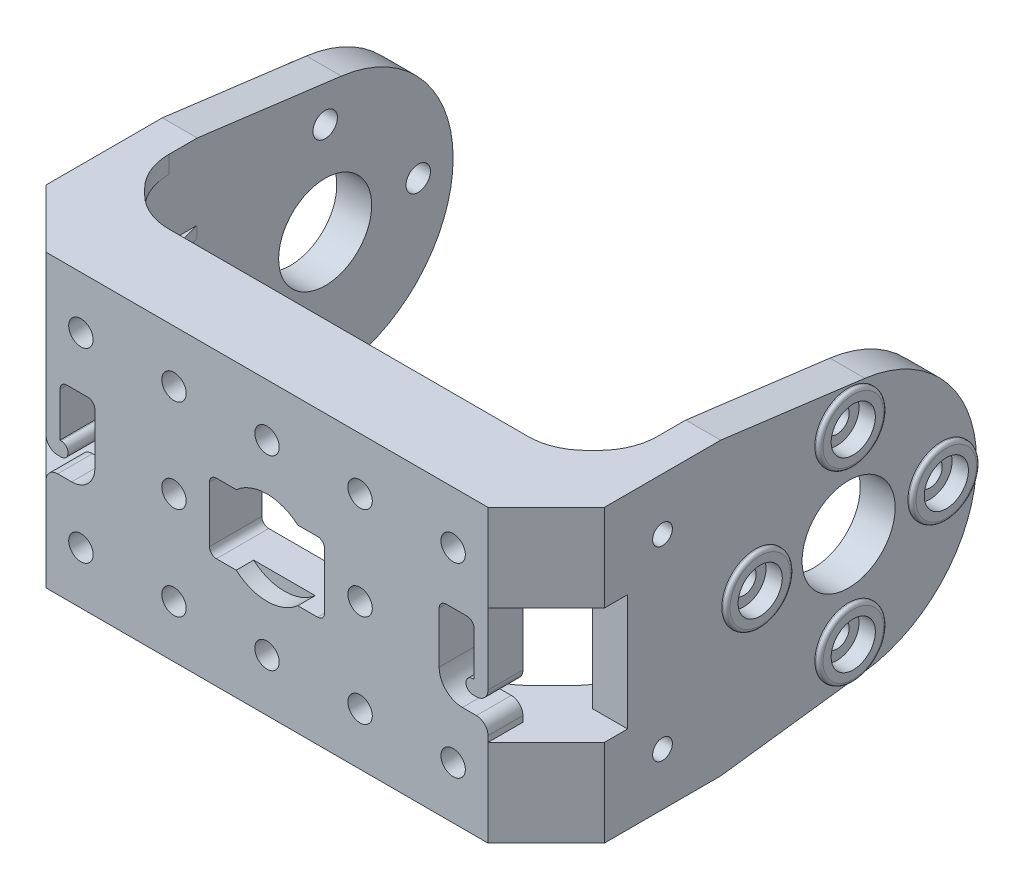
SolidWorks part; units mm, degrees
ref_plane "Plan de face" through (0, 0, 0) normal (0, 0, 1) x (1, 0, 0)
ref_plane "Plan de dessus" through (0, 0, 0) normal (0, 1, 0) x (1, 0, 0)
ref_plane "Plan de droite" through (0, 0, 0) normal (1, 0, 0) x (0, 0, -1)
ref_plane "Plan1" through (0, 0, 23) normal (0, 0, 1) x (1, 0, 0)
sketch "Esquisse1" plane through (0, 0, 23) normal (0, 0, 1) x (1, 0, 0)
  line L0 (14.5956, -5) -> (10.0809, -3.5)
  line L1 (10.0809, -3.5) -> (10.0809, -2.4936)
  line L2 (10.0809, -2.4936) -> (11.2, -1.8475)
  line L3 (11.2, -1.8475) -> (11.2, 1.8475)
  line L4 (11.2, 1.8475) -> (10.0809, 2.4936)
  line L5 (10.0809, 2.4936) -> (10.0809, 3.5)
  line L6 (10.0809, 3.5) -> (14.5956, 5)
  line L7 (14.5956, 5) -> (-14.5956, 5)
  line L8 (-14.5956, 5) -> (-10.0809, 3.5)
  line L9 (-10.0809, 3.5) -> (-10.0809, 2.4936)
  line L10 (-10.0809, 2.4936) -> (-11.2, 1.8475)
  line L11 (-11.2, 1.8475) -> (-11.2, -1.8475)
  line L12 (-11.2, -1.8475) -> (-10.0809, -2.4936)
  line L13 (-10.0809, -2.4936) -> (-10.0809, -3.5)
  line L14 (-10.0809, -3.5) -> (-14.5956, -5)
  line L15 (-14.5956, -5) -> (14.5956, -5)
extrude "Boss.-Extru.1" add sketch "Esquisse1" against normal blind 1
sketch "Esquisse2" plane through (0, 0, 22) normal (0, 0, -1) x (-1, 0, 0)
  line L0 (-14.5956, 5) -> (14.5956, 5)
  line L1 (14.5956, 5) -> (10.0809, 3.5)
  line L2 (10.0809, 3.5) -> (10.0809, -3.5)
  line L3 (10.0809, -3.5) -> (14.5956, -5)
  line L4 (14.5956, -5) -> (-14.5956, -5)
  line L5 (-14.5956, -5) -> (-10.0809, -3.5)
  line L6 (-10.0809, -3.5) -> (-10.0809, 3.5)
  line L7 (-10.0809, 3.5) -> (-14.5956, 5)
extrude "Boss.-Extru.2" add sketch "Esquisse2" along normal blind 0.5
sketch "Esquisse3" plane through (0, 0, 23) normal (0, 0, 1) x (1, 0, 0)
  line L0 (10.0809, 3.5) -> (8.3378, 3.5)
  line L1 (8.3378, 3.5) -> (10.0809, 2.4936)
  line L2 (10.0809, 2.4936) -> (10.0809, 3.5)
extrude "Enlèv. mat.-Extru.1" cut sketch "Esquisse3" against normal blind 1
sketch "Esquisse4" plane through (0, 0, 23) normal (0, 0, 1) x (1, 0, 0)
  line L0 (10.0809, -3.5) -> (10.0809, -2.4936)
  line L1 (10.0809, -2.4936) -> (8.3378, -3.5)
  line L2 (8.3378, -3.5) -> (10.0809, -3.5)
extrude "Enlèv. mat.-Extru.2" cut sketch "Esquisse4" against normal blind 1
sketch "Esquisse5" plane through (0, 0, 23) normal (0, 0, 1) x (1, 0, 0)
  line L0 (-10.0809, -3.5) -> (-8.3378, -3.5)
  line L1 (-8.3378, -3.5) -> (-10.0809, -2.4936)
  line L2 (-10.0809, -2.4936) -> (-10.0809, -3.5)
extrude "Enlèv. mat.-Extru.3" cut sketch "Esquisse5" against normal blind 1
sketch "Esquisse6" plane through (0, 0, 23) normal (0, 0, 1) x (1, 0, 0)
  line L0 (-10.0809, 3.5) -> (-10.0809, 2.4936)
  line L1 (-10.0809, 2.4936) -> (-8.3378, 3.5)
  line L2 (-8.3378, 3.5) -> (-10.0809, 3.5)
extrude "Enlèv. mat.-Extru.4" cut sketch "Esquisse6" against normal blind 1
sketch "Esquisse7" plane through (0, 5, 0) normal (0, 1, 0) x (-1, 0, 0)
  line L0 (21, 23) -> (21, 11)
  line L1 (21, 11) -> (19.5, 17.0147)
  line L2 (19.5, 17.0147) -> (17.5147, 19)
  line L3 (17.5147, 19) -> (-17.5147, 19)
  line L4 (-17.5147, 19) -> (-19.5, 17.0147)
  line L5 (-19.5, 17.0147) -> (-21, 11)
  line L6 (-21, 11) -> (-21, 23)
  line L7 (-21, 23) -> (21, 23)
extrude "Boss.-Extru.3" add sketch "Esquisse7" along normal blind 1
sketch "Esquisse8" plane through (0, -5, 0) normal (0, -1, 0) x (1, 0, 0)
  line L0 (-21, 11) -> (-21, 23)
  line L1 (-21, 23) -> (21, 23)
  line L2 (21, 23) -> (21, 11)
  line L3 (21, 11) -> (19.5, 17.0147)
  line L4 (19.5, 17.0147) -> (17.5147, 19)
  line L5 (17.5147, 19) -> (-17.5147, 19)
  line L6 (-17.5147, 19) -> (-19.5, 17.0147)
  line L7 (-19.5, 17.0147) -> (-21, 11)
extrude "Boss.-Extru.4" add sketch "Esquisse8" along normal blind 1
sketch "Esquisse9" plane through (0, 6, 0) normal (0, 1, 0) x (-1, 0, 0)
  line L0 (21, 23) -> (21, 11)
  line L1 (21, 11) -> (19.5, 17.0147)
  line L2 (19.5, 17.0147) -> (17.5147, 19)
  line L3 (17.5147, 19) -> (-17.5147, 19)
  line L4 (-17.5147, 19) -> (-19.5, 17.0147)
  line L5 (-19.5, 17.0147) -> (-21, 11)
  line L6 (-21, 11) -> (-21, 23)
  line L7 (-21, 23) -> (21, 23)
extrude "Boss.-Extru.5" add sketch "Esquisse9" along normal blind 5
sketch "Esquisse10" plane through (0, -6, 0) normal (0, -1, 0) x (1, 0, 0)
  line L0 (-21, 11) -> (-21, 23)
  line L1 (-21, 23) -> (21, 23)
  line L2 (21, 23) -> (21, 11)
  line L3 (21, 11) -> (19.5, 17.0147)
  line L4 (19.5, 17.0147) -> (17.5147, 19)
  line L5 (17.5147, 19) -> (-17.5147, 19)
  line L6 (-17.5147, 19) -> (-19.5, 17.0147)
  line L7 (-19.5, 17.0147) -> (-21, 11)
extrude "Boss.-Extru.6" add sketch "Esquisse10" along normal blind 5
sketch "Esquisse11" plane through (0, 11, 0) normal (0, 1, 0) x (-1, 0, 0)
  line L0 (21, 23) -> (21, 11)
  line L1 (21, 11) -> (19.5, 17.0147)
  line L2 (19.5, 17.0147) -> (17.5147, 19)
  line L3 (17.5147, 19) -> (-17.5147, 19)
  line L4 (-17.5147, 19) -> (-19.5, 17.0147)
  line L5 (-19.5, 17.0147) -> (-21, 11)
  line L6 (-21, 11) -> (-21, 23)
  line L7 (-21, 23) -> (21, 23)
extrude "Boss.-Extru.7" add sketch "Esquisse11" along normal blind 1.5
sketch "Esquisse12" plane through (0, 5, 0) normal (0, -1, 0) x (1, 0, 0)
  line L0 (-17.5147, 19) -> (17.5147, 19)
  line L1 (17.5147, 19) -> (15.0147, 21.5)
  line L2 (15.0147, 21.5) -> (-15.0147, 21.5)
  line L3 (-15.0147, 21.5) -> (-17.5147, 19)
extrude "Enlèv. mat.-Extru.5" cut sketch "Esquisse12" against normal blind 6
sketch "Esquisse13" plane through (0, -11, 0) normal (0, -1, 0) x (1, 0, 0)
  line L0 (-21, 11) -> (-21, 23)
  line L1 (-21, 23) -> (21, 23)
  line L2 (21, 23) -> (21, 11)
  line L3 (21, 11) -> (19.5, 17.0147)
  line L4 (19.5, 17.0147) -> (17.5147, 19)
  line L5 (17.5147, 19) -> (-17.5147, 19)
  line L6 (-17.5147, 19) -> (-19.5, 17.0147)
  line L7 (-19.5, 17.0147) -> (-21, 11)
extrude "Boss.-Extru.8" add sketch "Esquisse13" along normal blind 1.5
sketch "Esquisse14" plane through (-21, 0, 0) normal (-1, 0, 0) x (0, 0, 1)
  line L0 (23, 12.5) -> (23, 5)
  line L1 (23, 5) -> (19, 5)
  line L2 (19, 5) -> (19, -5)
  line L3 (19, -5) -> (23, -5)
  line L4 (23, -5) -> (23, -12.5)
  line L5 (23, -12.5) -> (11, -12.5)
  line L6 (11, -12.5) -> (-1.3986, -10.9107)
  line L7 (-1.3986, 10.9107) -> (11, 12.5)
  line L8 (11, 12.5) -> (23, 12.5)
  arc A0 (-1.3986, -10.9107) -> (-1.3986, 10.9107) centre (0, 0) cw
extrude "Boss.-Extru.9" add sketch "Esquisse14" along normal blind 3
sketch "Esquisse15" plane through (21, 0, 0) normal (1, 0, 0) x (0, 0, -1)
  line L0 (-23, 12.5) -> (-11, 12.5)
  line L1 (-11, 12.5) -> (1.3986, 10.9107)
  line L2 (1.3986, -10.9107) -> (-11, -12.5)
  line L3 (-11, -12.5) -> (-23, -12.5)
  line L4 (-23, -12.5) -> (-23, -5)
  line L5 (-23, -5) -> (-19, -5)
  line L6 (-19, -5) -> (-19, 5)
  line L7 (-19, 5) -> (-23, 5)
  line L8 (-23, 5) -> (-23, 12.5)
  arc A0 (1.3986, 10.9107) -> (1.3986, -10.9107) centre (0, 0) cw
extrude "Boss.-Extru.10" add sketch "Esquisse15" along normal blind 3
sketch "Esquisse16" plane through (0, -5, 0) normal (0, 1, 0) x (-1, 0, 0)
  line L0 (17.5147, 19) -> (15.0147, 21.5)
  line L1 (15.0147, 21.5) -> (-15.0147, 21.5)
  line L2 (-15.0147, 21.5) -> (-17.5147, 19)
  line L3 (-17.5147, 19) -> (17.5147, 19)
extrude "Enlèv. mat.-Extru.6" cut sketch "Esquisse16" against normal blind 6
sketch "Esquisse17" plane through (0, -12.5, 0) normal (0, -1, 0) x (1, 0, 0)
  line L0 (21, 15.5147) -> (19.5, 17.0147)
  line L1 (19.5, 17.0147) -> (21, 11)
  line L2 (21, 11) -> (21, 15.5147)
extrude "Enlèv. mat.-Extru.7" cut sketch "Esquisse17" against normal blind 1.5
sketch "Esquisse18" plane through (0, -12.5, 0) normal (0, -1, 0) x (1, 0, 0)
  line L0 (-19.5, 17.0147) -> (-21, 15.5147)
  line L1 (-21, 15.5147) -> (-21, 11)
  line L2 (-21, 11) -> (-19.5, 17.0147)
extrude "Enlèv. mat.-Extru.8" cut sketch "Esquisse18" against normal blind 1.5
sketch "Esquisse19" plane through (0, -11, 0) normal (0, -1, 0) x (1, 0, 0)
  line L0 (21, 22) -> (-21, 22)
  line L1 (-21, 22) -> (-21, 11)
  line L2 (-21, 11) -> (-19.5, 17.0147)
  line L3 (-19.5, 17.0147) -> (-15.0147, 21.5)
  line L4 (-15.0147, 21.5) -> (15.0147, 21.5)
  line L5 (15.0147, 21.5) -> (19.5, 17.0147)
  line L6 (19.5, 17.0147) -> (21, 11)
  line L7 (21, 11) -> (21, 22)
extrude "Enlèv. mat.-Extru.9" cut sketch "Esquisse19" against normal blind 5
sketch "Esquisse20" plane through (0, 12.5, 0) normal (0, 1, 0) x (-1, 0, 0)
  line L0 (-21, 11) -> (-19.5, 17.0147)
  line L1 (-19.5, 17.0147) -> (-21, 15.5147)
  line L2 (-21, 15.5147) -> (-21, 11)
extrude "Enlèv. mat.-Extru.10" cut sketch "Esquisse20" against normal blind 1.5
sketch "Esquisse21" plane through (0, 12.5, 0) normal (0, 1, 0) x (-1, 0, 0)
  line L0 (21, 11) -> (21, 15.5147)
  line L1 (21, 15.5147) -> (19.5, 17.0147)
  line L2 (19.5, 17.0147) -> (21, 11)
extrude "Enlèv. mat.-Extru.11" cut sketch "Esquisse21" against normal blind 1.5
sketch "Esquisse22" plane through (0, 11, 0) normal (0, 1, 0) x (-1, 0, 0)
  line L0 (21, 11) -> (21, 22)
  line L1 (21, 22) -> (-21, 22)
  line L2 (-21, 22) -> (-21, 11)
  line L3 (-21, 11) -> (-19.5, 17.0147)
  line L4 (-19.5, 17.0147) -> (-15.0147, 21.5)
  line L5 (-15.0147, 21.5) -> (15.0147, 21.5)
  line L6 (15.0147, 21.5) -> (19.5, 17.0147)
  line L7 (19.5, 17.0147) -> (21, 11)
extrude "Enlèv. mat.-Extru.12" cut sketch "Esquisse22" against normal blind 5
sketch "Esquisse23" plane through (-10.0809, 0, 0) normal (-1, 0, 0) x (0, 0, 1)
  line L0 (22, -3.5) -> (22, 3.5)
  line L1 (22, 3.5) -> (21.5, 3.5)
  line L2 (21.5, 3.5) -> (21.5, -3.5)
  line L3 (21.5, -3.5) -> (22, -3.5)
extrude "Enlèv. mat.-Extru.13" cut sketch "Esquisse23" against normal blind 1.7431
sketch "Esquisse24" plane through (10.0809, 0, 0) normal (1, 0, 0) x (0, 0, -1)
  line L0 (-22, 3.5) -> (-22, -3.5)
  line L1 (-22, -3.5) -> (-21.5, -3.5)
  line L2 (-21.5, -3.5) -> (-21.5, 3.5)
  line L3 (-21.5, 3.5) -> (-22, 3.5)
extrude "Enlèv. mat.-Extru.14" cut sketch "Esquisse24" against normal blind 1.7431
sketch "Esquisse25" plane through (-8.3378, 0, 0) normal (-1, 0, 0) x (0, 0, 1)
  line L0 (22, -3.5) -> (22, 3.5)
  line L1 (22, 3.5) -> (21.5, 3.5)
  line L2 (21.5, 3.5) -> (21.5, -3.5)
  line L3 (21.5, -3.5) -> (22, -3.5)
extrude "Enlèv. mat.-Extru.15" cut sketch "Esquisse25" against normal blind 2.3378
sketch "Esquisse26" plane through (8.3378, 0, 0) normal (1, 0, 0) x (0, 0, -1)
  line L0 (-22, 3.5) -> (-22, -3.5)
  line L1 (-22, -3.5) -> (-21.5, -3.5)
  line L2 (-21.5, -3.5) -> (-21.5, 3.5)
  line L3 (-21.5, 3.5) -> (-22, 3.5)
extrude "Enlèv. mat.-Extru.16" cut sketch "Esquisse26" against normal blind 2.3378
sketch "Esquisse27" plane through (0, 0, 23) normal (0, 0, 1) x (1, 0, 0)
  line L0 (14.8, -3.5) -> (19, -3.5)
  line L1 (19, -3.5) -> (19, -5)
  line L2 (19, -5) -> (24, -5)
  line L3 (24, -5) -> (24, -12.5)
  line L4 (24, -12.5) -> (-24, -12.5)
  line L5 (-24, -12.5) -> (-24, -5)
  line L6 (-24, -5) -> (-19, -5)
  line L7 (-19, -5) -> (-19, -3.5)
  line L8 (-19, -3.5) -> (-14.8, -3.5)
  line L9 (-14.8, -3.5) -> (-14.8, 3.5)
  line L10 (-14.8, 3.5) -> (-17.8, 3.5)
  line L11 (-17.8, 3.5) -> (-17.8, -0.9)
  line L12 (-17.8, -0.9) -> (-17.7, -0.9)
  line L13 (-17.7, -2.1) -> (-19, -2.1)
  line L14 (-19, -2.1) -> (-19, 5)
  line L15 (-19, 5) -> (-24, 5)
  line L16 (-24, 5) -> (-24, 12.5)
  line L17 (-24, 12.5) -> (24, 12.5)
  line L18 (24, 12.5) -> (24, 5)
  line L19 (24, 5) -> (19, 5)
  line L20 (19, 5) -> (19, -2.1)
  line L21 (19, -2.1) -> (17.7, -2.1)
  line L22 (17.7, -0.9) -> (17.8, -0.9)
  line L23 (17.8, -0.9) -> (17.8, 3.5)
  line L24 (17.8, 3.5) -> (14.8, 3.5)
  line L25 (14.8, 3.5) -> (14.8, -3.5)
  arc A0 (-17.7, -0.9) -> (-17.7, -2.1) centre (-17.7, -1.5) cw
  arc A1 (17.7, -2.1) -> (17.7, -0.9) centre (17.7, -1.5) cw
extrude "Boss.-Extru.11" add sketch "Esquisse27" along normal blind 3
sketch "Esquisse28" plane through (0, 0, 22) normal (0, 0, -1) x (-1, 0, 0)
  line L0 (13.6906, -6) -> (10.9359, -6)
  line L1 (10.9359, -6) -> (11.2, -6.1525)
  line L2 (11.2, -6.1525) -> (11.2, -9.8475)
  line L3 (11.2, -9.8475) -> (9.2038, -11)
  line L4 (9.2038, -11) -> (14.2679, -11)
  line L5 (14.2679, -11) -> (12.5359, -8)
  line L6 (12.5359, -8) -> (13.6906, -6)
extrude "Enlèv. mat.-Extru.17" cut sketch "Esquisse28" against normal blind 1
sketch "Esquisse29" plane through (0, 0, 21.5) normal (0, 0, -1) x (-1, 0, 0)
  line L0 (9.9191, -4.5) -> (-9.9191, -4.5)
  line L1 (-9.9191, -4.5) -> (-14.4338, -6)
  line L2 (-14.4338, -6) -> (14.4338, -6)
  line L3 (14.4338, -6) -> (9.9191, -4.5)
extrude "Enlèv. mat.-Extru.18" cut sketch "Esquisse29" against normal blind 1.5
sketch "Esquisse30" plane through (0, 0, 22) normal (0, 0, -1) x (-1, 0, 0)
  line L0 (-4.8, -6.1525) -> (-4.8, -9.8475)
  line L1 (-4.8, -9.8475) -> (-6.7962, -11)
  line L2 (-6.7962, -11) -> (-1.2038, -11)
  line L3 (-1.2038, -11) -> (-3.2, -9.8475)
  line L4 (-3.2, -9.8475) -> (-3.2, -6.1525)
  line L5 (-3.2, -6.1525) -> (-0.3378, -4.5)
  line L6 (-0.3378, -4.5) -> (-7.6622, -4.5)
  line L7 (-7.6622, -4.5) -> (-4.8, -6.1525)
extrude "Enlèv. mat.-Extru.19" cut sketch "Esquisse30" against normal blind 1
sketch "Esquisse31" plane through (0, 0, 22) normal (0, 0, -1) x (-1, 0, 0)
  line L0 (3.2, -6.1525) -> (3.2, -9.8475)
  line L1 (3.2, -9.8475) -> (1.2038, -11)
  line L2 (1.2038, -11) -> (6.7962, -11)
  line L3 (6.7962, -11) -> (4.8, -9.8475)
  line L4 (4.8, -9.8475) -> (4.8, -6.1525)
  line L5 (4.8, -6.1525) -> (7.6622, -4.5)
  line L6 (7.6622, -4.5) -> (0.3378, -4.5)
  line L7 (0.3378, -4.5) -> (3.2, -6.1525)
extrude "Enlèv. mat.-Extru.20" cut sketch "Esquisse31" against normal blind 1
sketch "Esquisse32" plane through (0, 0, 22) normal (0, 0, -1) x (-1, 0, 0)
  line L0 (-13.8102, -5.7928) -> (-12.5359, -8)
  line L1 (-12.5359, -8) -> (-14.2679, -11)
  line L2 (-14.2679, -11) -> (-9.2038, -11)
  line L3 (-9.2038, -11) -> (-11.2, -9.8475)
  line L4 (-11.2, -9.8475) -> (-11.2, -6.1525)
  line L5 (-11.2, -6.1525) -> (-8.3378, -4.5)
  line L6 (-8.3378, -4.5) -> (-9.9191, -4.5)
  line L7 (-9.9191, -4.5) -> (-13.8102, -5.7928)
extrude "Enlèv. mat.-Extru.21" cut sketch "Esquisse32" against normal blind 1
sketch "Esquisse33" plane through (0, 0, 21.5) normal (0, 0, -1) x (-1, 0, 0)
  line L0 (-9.9191, 4.5) -> (9.9191, 4.5)
  line L1 (9.9191, 4.5) -> (14.4338, 6)
  line L2 (14.4338, 6) -> (-14.4338, 6)
  line L3 (-14.4338, 6) -> (-9.9191, 4.5)
extrude "Enlèv. mat.-Extru.22" cut sketch "Esquisse33" against normal blind 0.5
sketch "Esquisse34" plane through (0, 0, 22) normal (0, 0, -1) x (-1, 0, 0)
  line L0 (13.8102, 5.7928) -> (12.5359, 8)
  line L1 (12.5359, 8) -> (14.2679, 11)
  line L2 (14.2679, 11) -> (9.2038, 11)
  line L3 (9.2038, 11) -> (11.2, 9.8475)
  line L4 (11.2, 9.8475) -> (11.2, 6.1525)
  line L5 (11.2, 6.1525) -> (8.3378, 4.5)
  line L6 (8.3378, 4.5) -> (9.9191, 4.5)
  line L7 (9.9191, 4.5) -> (13.8102, 5.7928)
extrude "Enlèv. mat.-Extru.23" cut sketch "Esquisse34" against normal blind 1
sketch "Esquisse35" plane through (0, 0, 22) normal (0, 0, -1) x (-1, 0, 0)
  line L0 (-3.2, 6.1525) -> (-3.2, 9.8475)
  line L1 (-3.2, 9.8475) -> (-1.2038, 11)
  line L2 (-1.2038, 11) -> (-6.7962, 11)
  line L3 (-6.7962, 11) -> (-4.8, 9.8475)
  line L4 (-4.8, 9.8475) -> (-4.8, 6.1525)
  line L5 (-4.8, 6.1525) -> (-7.6622, 4.5)
  line L6 (-7.6622, 4.5) -> (-0.3378, 4.5)
  line L7 (-0.3378, 4.5) -> (-3.2, 6.1525)
extrude "Enlèv. mat.-Extru.24" cut sketch "Esquisse35" against normal blind 1
sketch "Esquisse36" plane through (0, 0, 22) normal (0, 0, -1) x (-1, 0, 0)
  line L0 (-11.2, 6.1525) -> (-11.2, 9.8475)
  line L1 (-11.2, 9.8475) -> (-9.2038, 11)
  line L2 (-9.2038, 11) -> (-14.2679, 11)
  line L3 (-14.2679, 11) -> (-12.5359, 8)
  line L4 (-12.5359, 8) -> (-13.8102, 5.7928)
  line L5 (-13.8102, 5.7928) -> (-9.9191, 4.5)
  line L6 (-9.9191, 4.5) -> (-8.3378, 4.5)
  line L7 (-8.3378, 4.5) -> (-11.2, 6.1525)
extrude "Enlèv. mat.-Extru.25" cut sketch "Esquisse36" against normal blind 1
sketch "Esquisse37" plane through (0, 0, 22) normal (0, 0, -1) x (-1, 0, 0)
  line L0 (4.8, 6.1525) -> (4.8, 9.8475)
  line L1 (4.8, 9.8475) -> (6.7962, 11)
  line L2 (6.7962, 11) -> (1.2038, 11)
  line L3 (1.2038, 11) -> (3.2, 9.8475)
  line L4 (3.2, 9.8475) -> (3.2, 6.1525)
  line L5 (3.2, 6.1525) -> (0.3378, 4.5)
  line L6 (0.3378, 4.5) -> (7.6622, 4.5)
  line L7 (7.6622, 4.5) -> (4.8, 6.1525)
extrude "Enlèv. mat.-Extru.26" cut sketch "Esquisse37" against normal blind 1
sketch "Esquisse38" plane through (0, 0, 22) normal (0, 0, -1) x (-1, 0, 0)
  line L0 (17.1547, -10) -> (18.3094, -8)
  line L1 (18.3094, -8) -> (17.1547, -6)
  line L2 (17.1547, -6) -> (14.8453, -6)
  line L3 (14.8453, -6) -> (13.6906, -8)
  line L4 (13.6906, -8) -> (14.8453, -10)
  line L5 (14.8453, -10) -> (17.1547, -10)
extrude "Enlèv. mat.-Extru.27" cut sketch "Esquisse38" against normal blind 2
sketch "Esquisse39" plane through (0, 0, 22) normal (0, 0, -1) x (-1, 0, 0)
  line L0 (17.7321, -11) -> (21, -11)
  line L1 (21, -11) -> (21, -6)
  line L2 (21, -6) -> (18.3094, -6)
  line L3 (18.3094, -6) -> (19.4641, -8)
  line L4 (19.4641, -8) -> (17.7321, -11)
extrude "Enlèv. mat.-Extru.28" cut sketch "Esquisse39" against normal blind 1
sketch "Esquisse40" plane through (0, 0, 22) normal (0, 0, -1) x (-1, 0, 0)
  line L0 (-17.1547, -10) -> (-14.8453, -10)
  line L1 (-14.8453, -10) -> (-13.6906, -8)
  line L2 (-13.6906, -8) -> (-14.8453, -6)
  line L3 (-14.8453, -6) -> (-17.1547, -6)
  line L4 (-17.1547, -6) -> (-18.3094, -8)
  line L5 (-18.3094, -8) -> (-17.1547, -10)
extrude "Enlèv. mat.-Extru.29" cut sketch "Esquisse40" against normal blind 2
sketch "Esquisse41" plane through (0, 0, 22) normal (0, 0, -1) x (-1, 0, 0)
  line L0 (-21, -11) -> (-17.7321, -11)
  line L1 (-17.7321, -11) -> (-19.4641, -8)
  line L2 (-19.4641, -8) -> (-18.3094, -6)
  line L3 (-18.3094, -6) -> (-21, -6)
  line L4 (-21, -6) -> (-21, -11)
extrude "Enlèv. mat.-Extru.30" cut sketch "Esquisse41" against normal blind 1
sketch "Esquisse42" plane through (0, 0, 22) normal (0, 0, -1) x (-1, 0, 0)
  line L0 (-17.1547, 10) -> (-18.3094, 8)
  line L1 (-18.3094, 8) -> (-17.1547, 6)
  line L2 (-17.1547, 6) -> (-14.8453, 6)
  line L3 (-14.8453, 6) -> (-13.6906, 8)
  line L4 (-13.6906, 8) -> (-14.8453, 10)
  line L5 (-14.8453, 10) -> (-17.1547, 10)
extrude "Enlèv. mat.-Extru.31" cut sketch "Esquisse42" against normal blind 2
sketch "Esquisse43" plane through (0, 0, 22) normal (0, 0, -1) x (-1, 0, 0)
  line L0 (-17.7321, 11) -> (-21, 11)
  line L1 (-21, 11) -> (-21, 6)
  line L2 (-21, 6) -> (-18.3094, 6)
  line L3 (-18.3094, 6) -> (-19.4641, 8)
  line L4 (-19.4641, 8) -> (-17.7321, 11)
extrude "Enlèv. mat.-Extru.32" cut sketch "Esquisse43" against normal blind 1
sketch "Esquisse44" plane through (0, 0, 22) normal (0, 0, -1) x (-1, 0, 0)
  line L0 (17.1547, 10) -> (14.8453, 10)
  line L1 (14.8453, 10) -> (13.6906, 8)
  line L2 (13.6906, 8) -> (14.8453, 6)
  line L3 (14.8453, 6) -> (17.1547, 6)
  line L4 (17.1547, 6) -> (18.3094, 8)
  line L5 (18.3094, 8) -> (17.1547, 10)
extrude "Enlèv. mat.-Extru.33" cut sketch "Esquisse44" against normal blind 2
sketch "Esquisse45" plane through (0, 0, 22) normal (0, 0, -1) x (-1, 0, 0)
  line L0 (21, 11) -> (17.7321, 11)
  line L1 (17.7321, 11) -> (19.4641, 8)
  line L2 (19.4641, 8) -> (18.3094, 6)
  line L3 (18.3094, 6) -> (21, 6)
  line L4 (21, 6) -> (21, 11)
extrude "Enlèv. mat.-Extru.34" cut sketch "Esquisse45" against normal blind 1
sketch "Esquisse46" plane through (0, 0, 22) normal (0, 0, -1) x (-1, 0, 0)
  line L0 (10, -1.1547) -> (10, 1.1547)
  line L1 (10, 1.1547) -> (8, 2.3094)
  line L2 (8, 2.3094) -> (6, 1.1547)
  line L3 (6, 1.1547) -> (6, -1.1547)
  line L4 (6, -1.1547) -> (8, -2.3094)
  line L5 (8, -2.3094) -> (10, -1.1547)
extrude "Enlèv. mat.-Extru.35" cut sketch "Esquisse46" against normal blind 2
sketch "Esquisse47" plane through (0, 0, 22) normal (0, 0, -1) x (-1, 0, 0)
  line L0 (7.6622, -3.5) -> (6, -2.5403)
  line L1 (6, -2.5403) -> (6, -3.5)
  line L2 (6, -3.5) -> (7.6622, -3.5)
extrude "Enlèv. mat.-Extru.36" cut sketch "Esquisse47" against normal blind 1
sketch "Esquisse48" plane through (0, 0, 22) normal (0, 0, -1) x (-1, 0, 0)
  line L0 (7.6622, 3.5) -> (6, 3.5)
  line L1 (6, 3.5) -> (6, 2.5403)
  line L2 (6, 2.5403) -> (7.6622, 3.5)
extrude "Enlèv. mat.-Extru.37" cut sketch "Esquisse48" against normal blind 1
sketch "Esquisse49" plane through (0, 0, 22) normal (0, 0, -1) x (-1, 0, 0)
  line L0 (-6, -1.1547) -> (-6, 1.1547)
  line L1 (-6, 1.1547) -> (-8, 2.3094)
  line L2 (-8, 2.3094) -> (-10, 1.1547)
  line L3 (-10, 1.1547) -> (-10, -1.1547)
  line L4 (-10, -1.1547) -> (-8, -2.3094)
  line L5 (-8, -2.3094) -> (-6, -1.1547)
extrude "Enlèv. mat.-Extru.38" cut sketch "Esquisse49" against normal blind 2
sketch "Esquisse50" plane through (0, 0, 22) normal (0, 0, -1) x (-1, 0, 0)
  line L0 (-7.6622, 3.5) -> (-6, 2.5403)
  line L1 (-6, 2.5403) -> (-6, 3.5)
  line L2 (-6, 3.5) -> (-7.6622, 3.5)
extrude "Enlèv. mat.-Extru.39" cut sketch "Esquisse50" against normal blind 1
sketch "Esquisse51" plane through (0, 0, 22) normal (0, 0, -1) x (-1, 0, 0)
  line L0 (-7.6622, -3.5) -> (-6, -3.5)
  line L1 (-6, -3.5) -> (-6, -2.5403)
  line L2 (-6, -2.5403) -> (-7.6622, -3.5)
extrude "Enlèv. mat.-Extru.40" cut sketch "Esquisse51" against normal blind 1
sketch "Esquisse52" plane through (0, 0, 26) normal (0, 0, 1) x (1, 0, 0)
  line L0 (-4.95, 3) -> (-4.95, -3)
  line L1 (-4.95, -3) -> (4.95, -3)
  line L2 (4.95, -3) -> (4.95, 3)
  line L3 (4.95, 3) -> (-4.95, 3)
extrude "Enlèv. mat.-Extru.41" cut sketch "Esquisse52" against normal through all
sketch "Esquisse53" plane through (0, 0, 26) normal (0, 0, 1) x (1, 0, 0)
  line L0 (2.6458, -3) -> (-2.6458, -3)
  arc A0 (-2.6458, -3) -> (2.6458, -3) centre (0, 0) ccw
extrude "Enlèv. mat.-Extru.42" cut sketch "Esquisse53" against normal blind 1.5
sketch "Esquisse54" plane through (0, 0, 26) normal (0, 0, 1) x (1, 0, 0)
  line L0 (-2.6458, 3) -> (2.6458, 3)
  arc A0 (2.6458, 3) -> (-2.6458, 3) centre (0, 0) ccw
extrude "Enlèv. mat.-Extru.43" cut sketch "Esquisse54" against normal blind 1.5
sketch "Esquisse55" plane through (0, 0, 22) normal (0, 0, -1) x (-1, 0, 0)
  line L0 (0, -10.3094) -> (2, -9.1547)
  line L1 (2, -9.1547) -> (2, -6.8453)
  line L2 (2, -6.8453) -> (0, -5.6906)
  line L3 (0, -5.6906) -> (-2, -6.8453)
  line L4 (-2, -6.8453) -> (-2, -9.1547)
  line L5 (-2, -9.1547) -> (0, -10.3094)
extrude "Enlèv. mat.-Extru.44" cut sketch "Esquisse55" against normal blind 2
sketch "Esquisse56" plane through (0, 0, 22) normal (0, 0, -1) x (-1, 0, 0)
  line L0 (0, 5.6906) -> (2, 6.8453)
  line L1 (2, 6.8453) -> (2, 9.1547)
  line L2 (2, 9.1547) -> (0, 10.3094)
  line L3 (0, 10.3094) -> (-2, 9.1547)
  line L4 (-2, 9.1547) -> (-2, 6.8453)
  line L5 (-2, 6.8453) -> (0, 5.6906)
extrude "Enlèv. mat.-Extru.45" cut sketch "Esquisse56" against normal blind 2
sketch "Esquisse57" plane through (0, 0, 22) normal (0, 0, -1) x (-1, 0, 0)
  line L0 (-8, -10.3094) -> (-6, -9.1547)
  line L1 (-6, -9.1547) -> (-6, -6.8453)
  line L2 (-6, -6.8453) -> (-8, -5.6906)
  line L3 (-8, -5.6906) -> (-10, -6.8453)
  line L4 (-10, -6.8453) -> (-10, -9.1547)
  line L5 (-10, -9.1547) -> (-8, -10.3094)
extrude "Enlèv. mat.-Extru.46" cut sketch "Esquisse57" against normal blind 2
sketch "Esquisse58" plane through (0, 0, 22) normal (0, 0, -1) x (-1, 0, 0)
  line L0 (-8, 5.6906) -> (-6, 6.8453)
  line L1 (-6, 6.8453) -> (-6, 9.1547)
  line L2 (-6, 9.1547) -> (-8, 10.3094)
  line L3 (-8, 10.3094) -> (-10, 9.1547)
  line L4 (-10, 9.1547) -> (-10, 6.8453)
  line L5 (-10, 6.8453) -> (-8, 5.6906)
extrude "Enlèv. mat.-Extru.47" cut sketch "Esquisse58" against normal blind 2
sketch "Esquisse59" plane through (0, 0, 22) normal (0, 0, -1) x (-1, 0, 0)
  line L0 (8, 5.6906) -> (10, 6.8453)
  line L1 (10, 6.8453) -> (10, 9.1547)
  line L2 (10, 9.1547) -> (8, 10.3094)
  line L3 (8, 10.3094) -> (6, 9.1547)
  line L4 (6, 9.1547) -> (6, 6.8453)
  line L5 (6, 6.8453) -> (8, 5.6906)
extrude "Enlèv. mat.-Extru.48" cut sketch "Esquisse59" against normal blind 2
sketch "Esquisse60" plane through (0, 0, 22) normal (0, 0, -1) x (-1, 0, 0)
  line L0 (8, -10.3094) -> (10, -9.1547)
  line L1 (10, -9.1547) -> (10, -6.8453)
  line L2 (10, -6.8453) -> (8, -5.6906)
  line L3 (8, -5.6906) -> (6, -6.8453)
  line L4 (6, -6.8453) -> (6, -9.1547)
  line L5 (6, -9.1547) -> (8, -10.3094)
extrude "Enlèv. mat.-Extru.49" cut sketch "Esquisse60" against normal blind 2
sketch "Esquisse61" plane through (0, 0, 0) normal (0, 0, 1) x (1, 0, 0)
  line L0 (24, 10.9) -> (24, 8)
  line L1 (24, 8) -> (24.4, 8)
  line L2 (24.4, 8) -> (24.4, 10.9)
  line L3 (24.4, 10.9) -> (24, 10.9)
  line L4 (24, 8) -> (24.4, 8) construction
revolve "Révolution1" add sketch "Esquisse61" angle 360 about L4 reverse direction yes
ref_plane "Plan2" through (0, 0, -8) normal (0, 0, 1) x (1, 0, 0)
sketch "Esquisse62" plane through (0, 0, -8) normal (0, 0, 1) x (1, 0, 0)
  line L0 (24, 2.9) -> (24, 0)
  line L1 (24, 0) -> (24.4, 0)
  line L2 (24.4, 0) -> (24.4, 2.9)
  line L3 (24.4, 2.9) -> (24, 2.9)
  line L4 (24, 0) -> (24.4, 0) construction
revolve "Révolution2" add sketch "Esquisse62" angle 360 about L4 reverse direction yes
sketch "Esquisse63" plane through (0, 0, 0) normal (0, 0, 1) x (1, 0, 0)
  line L0 (24, -5.1) -> (24, -8)
  line L1 (24, -8) -> (24.4, -8)
  line L2 (24.4, -8) -> (24.4, -5.1)
  line L3 (24.4, -5.1) -> (24, -5.1)
  line L4 (24, -8) -> (24.4, -8) construction
revolve "Révolution3" add sketch "Esquisse63" angle 360 about L4 reverse direction yes
ref_plane "Plan3" through (0, 0, 8) normal (0, 0, 1) x (1, 0, 0)
sketch "Esquisse64" plane through (0, 0, 8) normal (0, 0, 1) x (1, 0, 0)
  line L0 (24, 2.9) -> (24, 0)
  line L1 (24, 0) -> (24.4, 0)
  line L2 (24.4, 0) -> (24.4, 2.9)
  line L3 (24.4, 2.9) -> (24, 2.9)
  line L4 (24, 0) -> (24.4, 0) construction
revolve "Révolution4" add sketch "Esquisse64" angle 360 about L4 reverse direction yes
ref_plane "Plan4" through (0, 0, -8) normal (0, 0, -1) x (-1, 0, 0)
sketch "Esquisse65" plane through (0, 0, -8) normal (0, 0, -1) x (-1, 0, 0)
  line L0 (24, 2.9) -> (24, 0)
  line L1 (24, 0) -> (24.4, 0)
  line L2 (24.4, 0) -> (24.4, 2.9)
  line L3 (24.4, 2.9) -> (24, 2.9)
  line L4 (24, 0) -> (24.4, 0) construction
revolve "Révolution5" add sketch "Esquisse65" angle 360 about L4 reverse direction yes
ref_plane "Plan5" through (0, 0, 0) normal (0, 0, -1) x (-1, 0, 0)
sketch "Esquisse66" plane through (0, 0, 0) normal (0, 0, -1) x (-1, 0, 0)
  line L0 (24, 10.9) -> (24, 8)
  line L1 (24, 8) -> (24.4, 8)
  line L2 (24.4, 8) -> (24.4, 10.9)
  line L3 (24.4, 10.9) -> (24, 10.9)
  line L4 (24, 8) -> (24.4, 8) construction
revolve "Révolution6" add sketch "Esquisse66" angle 360 about L4 reverse direction yes
ref_plane "Plan6" through (0, 0, 8) normal (0, 0, -1) x (-1, 0, 0)
sketch "Esquisse67" plane through (0, 0, 8) normal (0, 0, -1) x (-1, 0, 0)
  line L0 (24, 2.9) -> (24, 0)
  line L1 (24, 0) -> (24.4, 0)
  line L2 (24.4, 0) -> (24.4, 2.9)
  line L3 (24.4, 2.9) -> (24, 2.9)
  line L4 (24, 0) -> (24.4, 0) construction
revolve "Révolution7" add sketch "Esquisse67" angle 360 about L4 reverse direction yes
sketch "Esquisse68" plane through (0, 0, 0) normal (0, 0, -1) x (-1, 0, 0)
  line L0 (24, -5.1) -> (24, -8)
  line L1 (24, -8) -> (24.4, -8)
  line L2 (24.4, -8) -> (24.4, -5.1)
  line L3 (24.4, -5.1) -> (24, -5.1)
  line L4 (24, -8) -> (24.4, -8) construction
revolve "Révolution8" add sketch "Esquisse68" angle 360 about L4 reverse direction yes
hole_wizard "Diamètre du perçage Ø2.1 (2.1)1" positions "Esquisse70" profile "Esquisse69" hole size "Ø2.1" standard "Ansi Metric"
sketch "Esquisse70" plane through (0, 0, 24) normal (0, 0, -1) x (-1, 0, 0)
  point P0 (0, -8)
  point P1 (8, 0)
  point P2 (0, 8)
  point P3 (-8, 0)
  point P4 (-8, -8)
  point P5 (-8, 8)
  point P6 (8, 8)
  point P7 (8, -8)
  point P8 (16, -8)
  point P9 (16, 8)
  point P10 (-16, 8)
  point P11 (-16, -8)
sketch "Esquisse69" plane through (0, -8, 24) normal (1, 0, 0) x (0, 1, 0)
  line L0 (0, 0) -> (0, 2)
  line L1 (0, 2) -> (1.05, 2)
  line L2 (1.05, 2) -> (1.05, 0)
  line L5 (1.05, 0) -> (0, 0)
  line L11 (0, -6.35) -> (0, 107.95) construction
  dimension "Diamètre du perçage jusqu'au prochain" = 2.1
  dimension "Profondeur du perçage jusqu'au prochain" = 2
hole_wizard "Diamètre du perçage Ø1.7 (1.7)1" positions "Esquisse72" profile "Esquisse71" hole size "Ø1.7" standard "Ansi Metric"
sketch "Esquisse72" plane through (24, 0, 0) normal (1, 0, 0) x (0, 0, -1)
  point P0 (-16, -8)
  point P1 (-16, 8)
sketch "Esquisse71" plane through (24, -8, 16) normal (0, 1, 0) x (0, 0, -1)
  line L0 (0, 0) -> (0, 3)
  line L1 (0, 3) -> (0.85, 3)
  line L2 (0.85, 3) -> (0.85, 0)
  line L5 (0.85, 0) -> (0, 0)
  line L11 (0, -6.35) -> (0, 107.95) construction
  dimension "Diamètre du perçage jusqu'au prochain" = 1.7
  dimension "Profondeur du perçage jusqu'au prochain" = 3
hole_wizard "Diamètre du perçage Ø8.0 (8)1" positions "Esquisse74" profile "Esquisse73" hole size "Ø8.0" standard "Ansi Metric"
sketch "Esquisse74" plane through (24, 0, 0) normal (1, 0, 0) x (0, 0, -1)
  point P0 (0, 0)
sketch "Esquisse73" plane through (24, 0, 0) normal (0, 1, 0) x (0, 0, -1)
  line L0 (0, 0) -> (0, 3)
  line L1 (0, 3) -> (4, 3)
  line L2 (4, 3) -> (4, 0)
  line L5 (4, 0) -> (0, 0)
  line L11 (0, -6.35) -> (0, 107.95) construction
  dimension "Diamètre du perçage jusqu'au prochain" = 8
  dimension "Profondeur du perçage jusqu'au prochain" = 3
hole_wizard "Diamètre du perçage Ø1.7 (1.7)2" positions "Esquisse76" profile "Esquisse75" hole size "Ø1.7" standard "Ansi Metric"
sketch "Esquisse76" plane through (-24, 0, 0) normal (-1, 0, 0) x (0, 0, 1)
  point P0 (16, -8)
  point P1 (16, 8)
sketch "Esquisse75" plane through (-24, -8, 16) normal (0, 1, 0) x (0, 0, 1)
  line L0 (0, 0) -> (0, 48.4)
  line L1 (0, 48.4) -> (0.85, 48.4)
  line L2 (0.85, 48.4) -> (0.85, 0)
  line L5 (0.85, 0) -> (0, 0)
  line L11 (0, -6.35) -> (0, 107.95) construction
  dimension "Diamètre du perçage jusqu'au prochain" = 1.7
  dimension "Profondeur du perçage jusqu'au prochain" = 48.4
hole_wizard "Diamètre du perçage Ø8.0 (8)2" positions "Esquisse78" profile "Esquisse77" hole size "Ø8.0" standard "Ansi Metric"
sketch "Esquisse78" plane through (-24, 0, 0) normal (-1, 0, 0) x (0, 0, 1)
  point P0 (0, 0)
sketch "Esquisse77" plane through (-24, 0, 0) normal (0, 1, 0) x (0, 0, 1)
  line L0 (0, 0) -> (0, 48.4)
  line L1 (0, 48.4) -> (4, 48.4)
  line L2 (4, 48.4) -> (4, 0)
  line L5 (4, 0) -> (0, 0)
  line L11 (0, -6.35) -> (0, 107.95) construction
  dimension "Diamètre du perçage jusqu'au prochain" = 8
  dimension "Profondeur du perçage jusqu'au prochain" = 48.4
hole_wizard "Perçage1" positions "Esquisse80" profile "Esquisse79" legacy
sketch "Esquisse80" plane through (24.4, 0, 0) normal (1, 0, 0) x (0, 0, -1)
  point P0 (-8, 0)
  point P1 (0, 8)
  point P2 (8, 0)
  point P3 (0, -8)
sketch "Esquisse79" plane through (24.4, 0, 8) normal (0, 1, 0) x (0, 0, -1)
  line L0 (0, 0) -> (0, 3.4)
  line L1 (0, 3.4) -> (1.05, 3.4)
  line L2 (1.05, 3.4) -> (1.05, 1.4)
  line L3 (1.05, 1.4) -> (1.9, 1.4)
  line L4 (1.9, 1.4) -> (1.9, 0)
  line L5 (1.9, 0) -> (0, 0)
  line L6 (0, 110) -> (0, -10) construction
  dimension "Diamètre" = 2.1
  dimension "Profondeur" = 3.4
  dimension "Diamètre chambrage" = 3.8
  dimension "Profondeur chambrage" = 1.4
hole_wizard "Perçage2" positions "Esquisse82" profile "Esquisse81" legacy
sketch "Esquisse82" plane through (-24.4, 0, 0) normal (-1, 0, 0) x (0, 0, 1)
  point P0 (8, 0)
  point P1 (0, 8)
  point P2 (-8, 0)
  point P3 (0, -8)
sketch "Esquisse81" plane through (-24.4, 0, 8) normal (0, 1, 0) x (0, 0, 1)
  line L0 (0, 0) -> (0, 48.8)
  line L1 (0, 48.8) -> (1.05, 48.8)
  line L2 (1.05, 48.8) -> (1.05, 1.4)
  line L3 (1.05, 1.4) -> (1.9, 1.4)
  line L4 (1.9, 1.4) -> (1.9, 0)
  line L5 (1.9, 0) -> (0, 0)
  line L6 (0, 110) -> (0, -10) construction
  dimension "Diamètre" = 2.1
  dimension "Profondeur" = 48.8
  dimension "Diamètre chambrage" = 3.8
  dimension "Profondeur chambrage" = 1.4
chamfer "Chanfrein1" distance 5 angle 45 4 edges at (24, 8.75, 26) (-24, -8.75, 26) (-24, 8.75, 26) (24, -8.75, 26)
fillet "Congé1" radius 0.3 8 edges at (24.4, 8, -2.9) (24.4, -8, -2.9) (24.4, 0, 5.1) (-24.4, -8, 2.9) (24.4, 0, -10.9) (-24.4, 0, 10.9) (-24.4, 0, -5.1) (-24.4, 8, 2.9) tangent propagation no
fillet "Congé2" radius 0.6 8 edges at (-4.95, -3, 23.75) (4.95, -3, 23.75) (-4.95, 3, 23.75) (4.95, 3, 23.75) (17.8, 3.5, 24.5) (14.8, 3.5, 24.5) (-17.8, 3.5, 24.5) (-14.8, 3.5, 24.5) tangent propagation no
fillet "Congé3" radius 1 4 edges at (19, -2.1, 24.5) (-19, -3.5, 24.5) (19, -3.5, 24.5) (-19, -2.1, 24.5) tangent propagation no
fillet "Congé4" radius 2 2 edges at (14.8, -3.5, 24.5) (-14.8, -3.5, 24.5) tangent propagation no
fillet "Congé5" radius 5 16 edges at (21, -11.75, 15.5147) (21, 11.75, 15.5147) (-17.5147, 11.75, 19) (15.0147, 5.5, 21.5) (-17.5147, -11.75, 19) (19.5, 5.5, 17.0147) (17.5147, 11.75, 19) (-15.0147, 5.5, 21.5) (-21, 11.75, 15.5147) (-19.5, 5.5, 17.0147) (-21, -11.75, 15.5147) (-15.0147, -5.5, 21.5) (17.5147, -11.75, 19) (19.5, -5.5, 17.0147) (15.0147, -5.5, 21.5) (-19.5, -5.5, 17.0147) tangent propagation no
